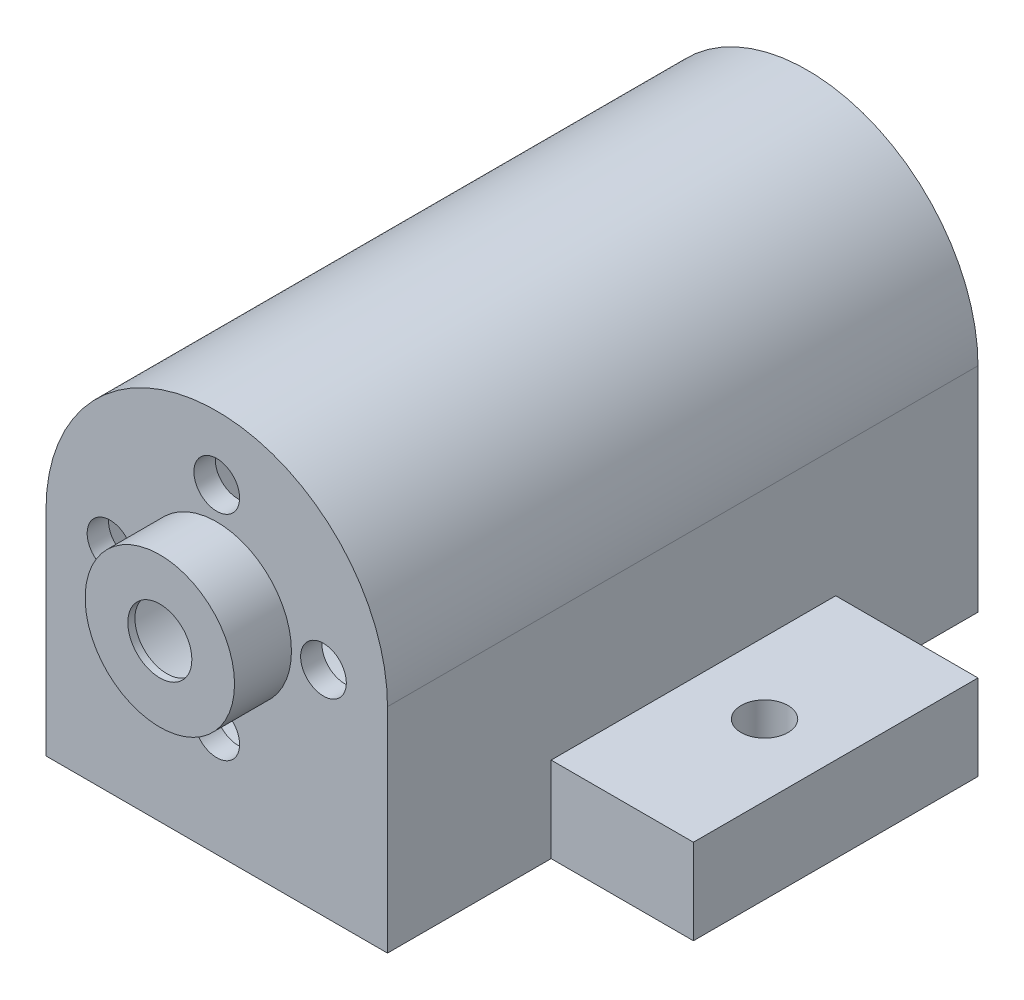
SolidWorks part; units mm, degrees
ref_plane "Alzado" through (0, 0, 0) normal (0, 0, 1) x (1, 0, 0)
ref_plane "Planta" through (0, 0, 0) normal (0, 1, 0) x (1, 0, 0)
ref_plane "Vista lateral" through (0, 0, 0) normal (1, 0, 0) x (0, 0, -1)
sketch "Croquis1" plane through (0, 0, 0) normal (0, 0, 1) x (1, 0, 0)
  circle A0 centre (-728.4228, 1.4092) radius 12
  dimension "D1" = 24
extrude "Saliente-Extruir1" add sketch "Croquis1" along normal blind 1.5
sketch "Croquis2" plane through (0, 0, 1.5) normal (0, 0, 1) x (1, 0, 0)
  line L0 (-728.4228, 13.4092) -> (-728.4228, -10.5908) construction
  line L1 (-728.4228, 1.4092) -> (-728.4228, 8.6968) construction
  line L2 (-728.4228, 1.4092) -> (-728.4228, 8.9092)
  circle A0 centre (-728.4228, 1.4092) radius 12 construction
  circle A1 centre (-728.4228, 8.9092) radius 1.6066
  circle A2 centre (-720.9228, 1.4092) radius 1.6066
  circle A3 centre (-728.4228, -6.0908) radius 1.6066
  circle A4 centre (-735.9228, 1.4092) radius 1.6066
  point P17 (-728.4228, 1.4092)
  dimension "D2" = 3.2132
  dimension "D1" = 7.5
  dimension "D3" = 4
extrude "Cortar-Extruir1" cut sketch "Croquis2" against normal blind 2 contours A1 | A2 | A3 | A4 region at (-727.3189, 7.8053, 1.5) region at (-720.9228, 1.4092, 1.5) region at (-728.4228, -6.0908, 1.5) region at (-735.9228, 1.4092, 1.5)
sketch "Croquis3" plane through (0, 0, 1.5) normal (0, 0, 1) x (1, 0, 0)
  line L0 (-728.4228, 13.4092) -> (-728.4228, 1.4092) construction
  circle A0 centre (-728.4228, 1.4092) radius 12 construction
  circle A1 centre (-728.4228, 1.4092) radius 5.25
  dimension "D1" = 10.5
extrude "Saliente-Extruir2" add sketch "Croquis3" along normal blind 4
sketch "Croquis4" plane through (0, 0, 0) normal (0, 0, -1) x (-1, 0, 0)
  line L0 (740.4228, 1.4092) -> (728.4228, 1.4092) construction
  circle A0 centre (728.4228, 1.4092) radius 12 construction
  circle A1 centre (728.4228, 1.4092) radius 5.1
  dimension "D1" = 10.2
extrude "Cortar-Extruir2" cut sketch "Croquis4" against normal blind 5
sketch "Croquis5" plane through (0, 0, 5.5) normal (0, 0, 1) x (1, 0, 0)
  line L0 (-723.1728, 1.4092) -> (-728.4228, 1.4092) construction
  circle A0 centre (-728.4228, 1.4092) radius 5.25 construction
  circle A1 centre (-728.4228, 1.4092) radius 2.25
  dimension "D1" = 4.5
extrude "Cortar-Extruir3" cut sketch "Croquis5" against normal blind 5
sketch "Croquis7" plane through (0, 0, 0) normal (0, 0, -1) x (-1, 0, 0)
  line L0 (733.5228, 1.4092) -> (728.4228, 1.4092) construction
  circle A0 centre (728.4228, 1.4092) radius 5.1 construction
  circle A1 centre (728.4228, 1.4092) radius 11.25
  circle A2 centre (728.4228, 1.4092) radius 12
  dimension "D1" = 22.5
extrude "Saliente-Extruir3" add sketch "Croquis7" along normal blind 40
sketch "Croquis8" plane through (0, 0, -40) normal (0, 0, -1) x (-1, 0, 0)
  line L0 (740.4228, 1.4092) -> (728.4228, 1.4092) construction
  line L1 (716.4228, 1.4092) -> (716.4228, -13.5908)
  line L2 (716.4228, -13.5908) -> (728.4228, -13.5908)
  line L3 (740.4228, 1.4092) -> (740.4228, -13.5908)
  line L4 (740.4228, -13.5908) -> (728.4228, -13.5908)
  circle A0 centre (728.4228, 1.4092) radius 12 construction
  arc A1 (716.4228, 1.4092) -> (740.4228, 1.4092) centre (728.4228, 1.4092) ccw
  dimension "D1" = 15
extrude "Saliente-Extruir4" add sketch "Croquis8" against normal blind 41.5
sketch "Croquis9" plane through (-740.4228, 0, 0) normal (-1, 0, 0) x (0, 0, 1)
  line L0 (-40, -13.5908) -> (-30.15, -13.5908) construction
  line L1 (1.5, -13.5908) -> (-40, -13.5908) construction
  line L2 (-40, -13.5908) -> (-40, 1.4092) construction
  line L3 (-40, -13.5908) -> (-30, -13.5908)
  line L4 (-30, -13.5908) -> (-10, -13.5908)
  line L5 (-30, -13.5908) -> (-30, -7.5908)
  line L6 (-30, -7.5908) -> (-10, -7.5908)
  line L7 (-10, -7.5908) -> (-10, -13.5908)
  dimension "D1" = 10
  dimension "D2" = 20
  dimension "D3" = 6
extrude "Saliente-Extruir5" add sketch "Croquis9" along normal blind 10 contours L5 L6 L7 L4
sketch "Croquis10" plane through (-716.4228, 0, 0) normal (1, 0, 0) x (0, 0, -1)
  line L0 (40, -13.5908) -> (30, -13.5908)
  line L1 (40, 1.4092) -> (40, -13.5908) construction
  line L2 (-1.5, -13.5908) -> (40, -13.5908) construction
  line L3 (30, -13.5908) -> (10, -13.5908)
  line L4 (10, -13.5908) -> (10, -7.5908)
  line L5 (10, -7.5908) -> (30, -7.5908)
  line L6 (30, -7.5908) -> (30, -13.5908)
  dimension "D1" = 10
  dimension "D2" = 6
extrude "Saliente-Extruir6" add sketch "Croquis10" along normal blind 10 contours L3 L4 L5 L6
sketch "Croquis11" plane through (0, -7.5908, 0) normal (0, 1, 0) x (1, 0, 0)
  line L0 (-740.4228, 30) -> (-740.4228, 10) construction
  line L1 (-740.4228, -1.5) -> (-740.4228, 40) construction
  line L2 (-740.4228, 10) -> (-740.4228, 20) construction
  line L3 (-740.4228, 20) -> (-750.4228, 20) construction
  line L4 (-750.4228, 30) -> (-750.4228, 10) construction
  line L5 (-750.4228, 20) -> (-745.4228, 20) construction
  line L6 (-745.4228, 20) -> (-745.4228, 30) construction
  line L7 (-750.4228, 30) -> (-740.4228, 30) construction
  line L8 (-706.4228, 10) -> (-706.4228, 30) construction
  line L9 (-706.4228, 10) -> (-716.4228, 10) construction
  line L10 (-706.4228, 10) -> (-706.4228, 30) construction
  line L11 (-706.4228, 30) -> (-706.4228, 20) construction
  line L12 (-706.4228, 20) -> (-716.4228, 20) construction
  line L13 (-716.4228, 10) -> (-716.4228, 30) construction
  line L14 (-716.4228, 20) -> (-711.4228, 20) construction
  circle A0 centre (-745.4228, 20) radius 1.65
  circle A1 centre (-711.4228, 20) radius 1.65
  dimension "D1" = 3.3
  dimension "D2" = 3.3
extrude "Cortar-Extruir4" cut sketch "Croquis11" against normal blind 10
sketch "Croquis12" plane through (0, -7.5908, 0) normal (0, 1, 0) x (1, 0, 0)
  line L0 (-728.4228, -5.5) -> (-700.3951, -5.5) construction
  line L1 (-733.6728, -5.5) -> (-723.1728, -5.5) construction
  line L2 (-711.4228, 20) -> (-711.4228, -5.5)
  line L3 (-711.4228, -5.5) -> (-728.4228, -5.5)
  line L4 (-711.4228, 20) -> (-716.4228, 20)
  line L5 (-716.4228, 10) -> (-716.4228, 30) construction
  line L6 (-716.4228, 20) -> (-716.4228, -1.5)
  line L7 (-716.4228, -1.5) -> (-716.4228, 10)
  dimension "D1" = 25.5
  dimension "D2" = 17
  dimension "D3" = 21.5
